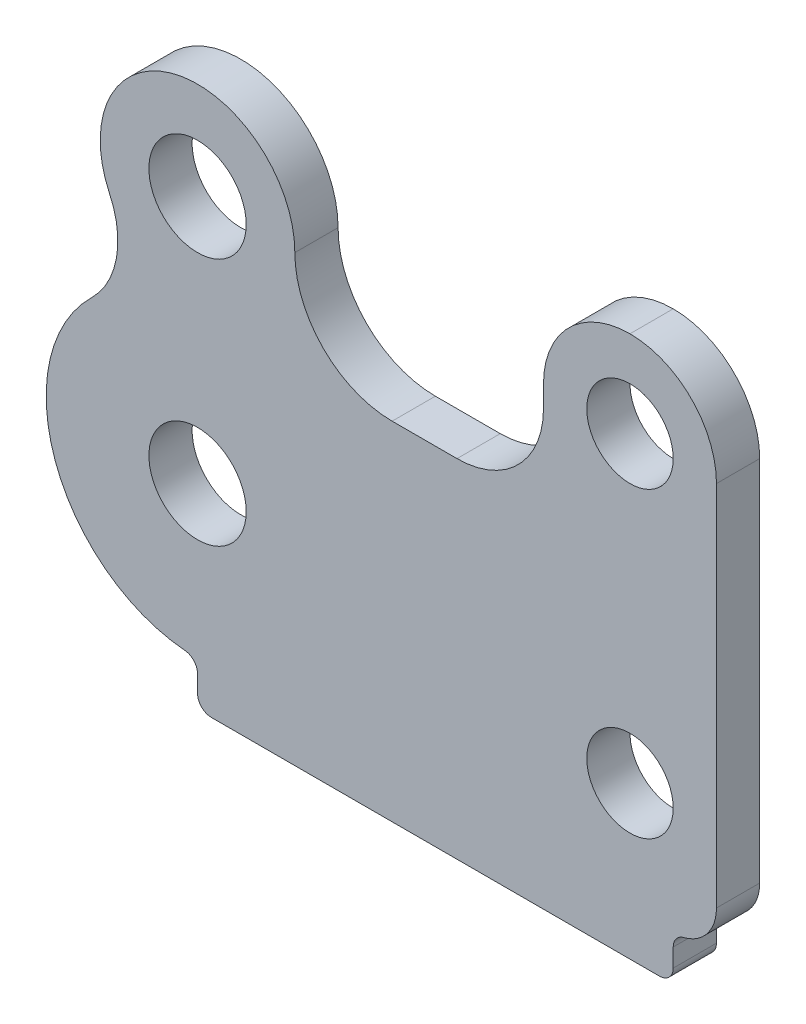
SolidWorks part; units mm, degrees
ref_plane "Front Plane" through (0, 0, 0) normal (0, 0, 1) x (1, 0, 0)
ref_plane "Top Plane" through (0, 0, 0) normal (0, 1, 0) x (1, 0, 0)
ref_plane "Right Plane" through (0, 0, 0) normal (1, 0, 0) x (0, 0, -1)
sketch "Sketch2" plane through (0, 0, 0) normal (0, 0, 1) x (1, 0, 0)
  line L0 (0, 5.5562) -> (12.7, 5.5562)
  line L1 (12.7, 5.5562) -> (12.7, -5.5562) construction
  line L2 (12.7, -5.5562) -> (0, -5.5562)
  line L3 (12.7, 5.5562) -> (12.7, 13.4938)
  line L4 (12.7, 13.4938) -> (19.05, 13.4937)
  line L5 (19.05, 13.4937) -> (19.05, -5.5562)
  line L6 (19.05, -5.5562) -> (12.7, -5.5562)
  line L7 (15.875, 9.525) -> (15.875, -1.5875) construction
  line L8 (0, -5.5562) -> (0, -7.1818)
  line L9 (0, -7.1818) -> (17.4625, -7.1818)
  line L10 (17.4625, -7.1818) -> (17.4625, -5.5562)
  line L11 (0, 0) -> (0, -9.1281) construction
  line L12 (7.1437, 12.7) -> (12.7, 12.7)
  line L14 (12.7, 12.7) -> (19.05, 12.7)
  line L15 (0, 12.7) -> (7.1437, 12.7)
  circle A0 centre (0, 0) radius 1.7859
  circle A1 centre (0, 0) radius 5.5562
  circle A2 centre (0, 9.1281) radius 1.7859
  circle A3 centre (0, 9.1281) radius 3.5719
  circle A4 centre (0, 0) radius 9.1281 construction
  circle A5 centre (15.875, 9.525) radius 1.5875
  circle A6 centre (15.875, -1.5875) radius 1.5875
  circle A7 centre (-6.1005, 6.2465) radius 3.175
  circle A8 centre (7.1437, 9.1281) radius 3.5719
  circle A9 centre (0, 0) radius 12.7 construction
  circle A11 centre (7.1437, 9.1281) radius 1.7859 construction
  point P17 (15.875, 3.9688)
  point P18 (19.05, 3.9688)
  point P21 (15.875, -5.5562)
  point P22 (17.747, -5.5562)
  point P38 (14.2875, -7.1818)
  point P39 (-0.2225, -5.5518)
  dimension "D1" = 3.5719
  dimension "D2" = 11.1125
  dimension "D5" = 7.1437
  dimension "D7" = 3.175
  dimension "D6" = 6.35
  dimension "D3" = 11.1125
  dimension "D4" = 6.35
  dimension "D8" = 1.5875
  dimension "D9" = 1.6256
  dimension "D10" = 19.05
extrude "Boss-Extrude1" add sketch "Sketch2" along normal blind 1.5875 contours A1 L2 L6 L5 L4 L3 L0 A6 A5 | L9 L10 L6 L8 | A8 A3 L0 | A1 A0 | A7 A1 A3 | A3 A2 region at (3.5719, 6.3541, 0) region at (12.3012, 1.8224, 0) region at (3.8177, 3.8177, 0) region at (-1.8576, 6.1962, 0) region at (-2.3434, 5.6656, 0) region at (8.7313, -6.369, 0)
fillet "Fillet1" radius 3.175 3 edges at (12.7, 5.5562, 0.7937) (12.7, 12.7, 0.7937) (19.05, 12.7, 0.7937)
fillet "Fillet3" radius 1.5875 1 edges at (19.05, -5.5562, 0.7937)
fillet "Fillet2" radius 0.508 4 edges at (0, -7.1818, 0.7937) (17.4625, -7.1818, 0.7937) (17.4625, -5.5562, 0.7937) (0, -5.5562, 0.7937)
